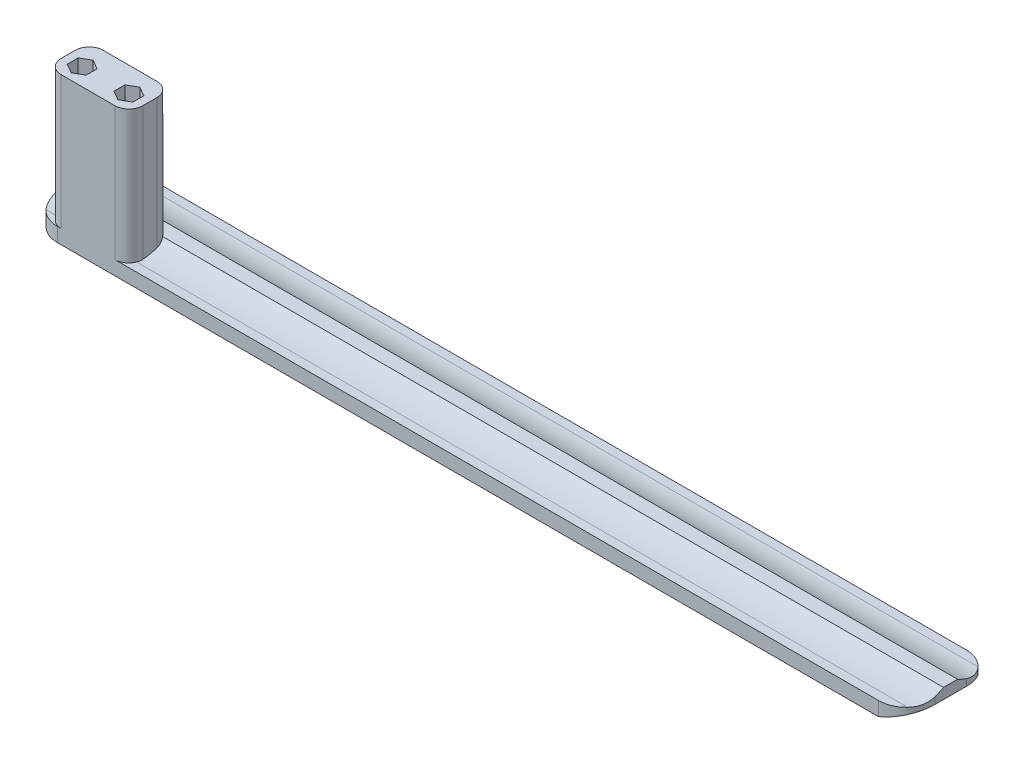
SolidWorks part; units mm, degrees
ref_plane "Front Plane" through (0, 0, 0) normal (0, 0, 1) x (1, 0, 0)
ref_plane "Top Plane" through (0, 0, 0) normal (0, 1, 0) x (1, 0, 0)
ref_plane "Right Plane" through (0, 0, 0) normal (1, 0, 0) x (0, 0, -1)
sketch "Sketch1" plane through (0, 0, 0) normal (0, 1, 0) x (1, 0, 0)
  line L1 (-12.7, 25.4) -> (304.8, 25.4)
  line L2 (-12.7, 25.4) -> (-12.7, -6.35)
  line L3 (-12.7, -6.35) -> (304.8, -6.35)
  line L4 (304.8, 25.4) -> (304.8, -6.35)
  circle A0 centre (0, 0) radius 2.286
  circle A1 centre (16.9118, 0) radius 2.286
  point P9 (16.9118, 0)
  point P10 (0, 0)
  dimension "D3" = 4.572
  dimension "D1" = 12.7
  dimension "D2" = 31.75
  dimension "D4" = 317.5
  dimension "D5" = 6.35
extrude "Boss-Extrude1" add sketch "Sketch1" along normal blind 5.08 contours L4 L1 L2 L3 A1 A0 region at (146.4996, 0, -9.5561)
sketch "Sketch2" plane through (-12.7, 0, 0) normal (-1, 0, 0) x (0, 0, 1)
  line L0 (-25.4, 5.08) -> (6.35, 5.08) construction
  line L1 (-6.985, 5.08) -> (-12.065, 5.08)
  line L2 (-6.985, 5.08) -> (-6.985, 7.62)
  line L3 (-6.985, 7.62) -> (-12.065, 7.62)
  line L4 (-12.065, 5.08) -> (-12.065, 7.62)
  point P4 (-6.35, 5.08)
  point P7 (-9.525, 5.08)
  dimension "D1" = 5.08
  dimension "D2" = 2.54
extrude "Boss-Extrude2" add sketch "Sketch2" against normal up to surface (317.5 mm away) up to face at (304.8, 2.54, -9.525)
sketch "Sketch3" plane through (0, 5.08, 0) normal (0, 1, 0) x (1, 0, 0)
  line L1 (0, 3.9595) -> (-3.429, 1.9797)
  line L2 (-3.429, 1.9797) -> (-3.429, -1.9797)
  line L3 (-3.429, -1.9797) -> (0, -3.9595)
  line L4 (0, -3.9595) -> (3.429, -1.9797)
  line L5 (3.429, -1.9797) -> (3.429, 1.9797)
  line L6 (3.429, 1.9797) -> (0, 3.9595)
  line L7 (16.9118, 3.9595) -> (13.4828, 1.9797)
  line L8 (13.4828, 1.9797) -> (13.4828, -1.9797)
  line L9 (13.4828, -1.9797) -> (16.9118, -3.9595)
  line L10 (16.9118, -3.9595) -> (20.3408, -1.9797)
  line L11 (20.3408, -1.9797) -> (20.3408, 1.9797)
  line L12 (20.3408, 1.9797) -> (16.9118, 3.9595)
  line L13 (-6.35, -6.35) -> (23.2618, -6.35)
  line L14 (-6.35, -6.35) -> (-6.35, 8.89)
  line L15 (-6.35, 8.89) -> (23.2618, 8.89)
  line L16 (23.2618, -6.35) -> (23.2618, 8.89)
  line L17 (-12.7, -6.35) -> (304.8, -6.35) construction
  circle A0 centre (0, 0) radius 3.429 construction
  circle A1 centre (16.9118, 0) radius 3.429 construction
  point P25 (-9.7748, -5.5775)
  point P26 (-8.1356, -6.35)
  dimension "D1" = 6.858
  dimension "D2" = 6.35
  dimension "D3" = 6.35
  dimension "D4" = 8.89
extrude "Boss-Extrude3" add sketch "Sketch3" along normal blind 48.26
chamfer "Chamfer1" distance 3.81 angle 70 1 edges at (304.8, 0, -9.525) first distance on face at (304.8, 4.445, -9.525)
fillet "Fillet1" radius 5.08 4 edges at (23.2618, 30.48, -8.89) (23.2618, 29.21, 6.35) (-6.35, 29.21, 6.35) (-6.35, 30.48, -8.89)
fillet "Fillet2" radius 10.16 4 edges at (304.8, 4.445, 6.35) (304.8, 4.445, -25.4) (-12.7, 2.54, -25.4) (-12.7, 2.54, 6.35)
fillet "Fillet3" radius 21.59 3 edges at (-8.9678, 5.08, -6.985) (163.4737, 5.08, -6.985) (146.05, 5.08, -12.065)
fillet "Fillet4" radius 11.43 rebuild error yes
fillet "Fillet5" radius 11.43 rebuild error yes
